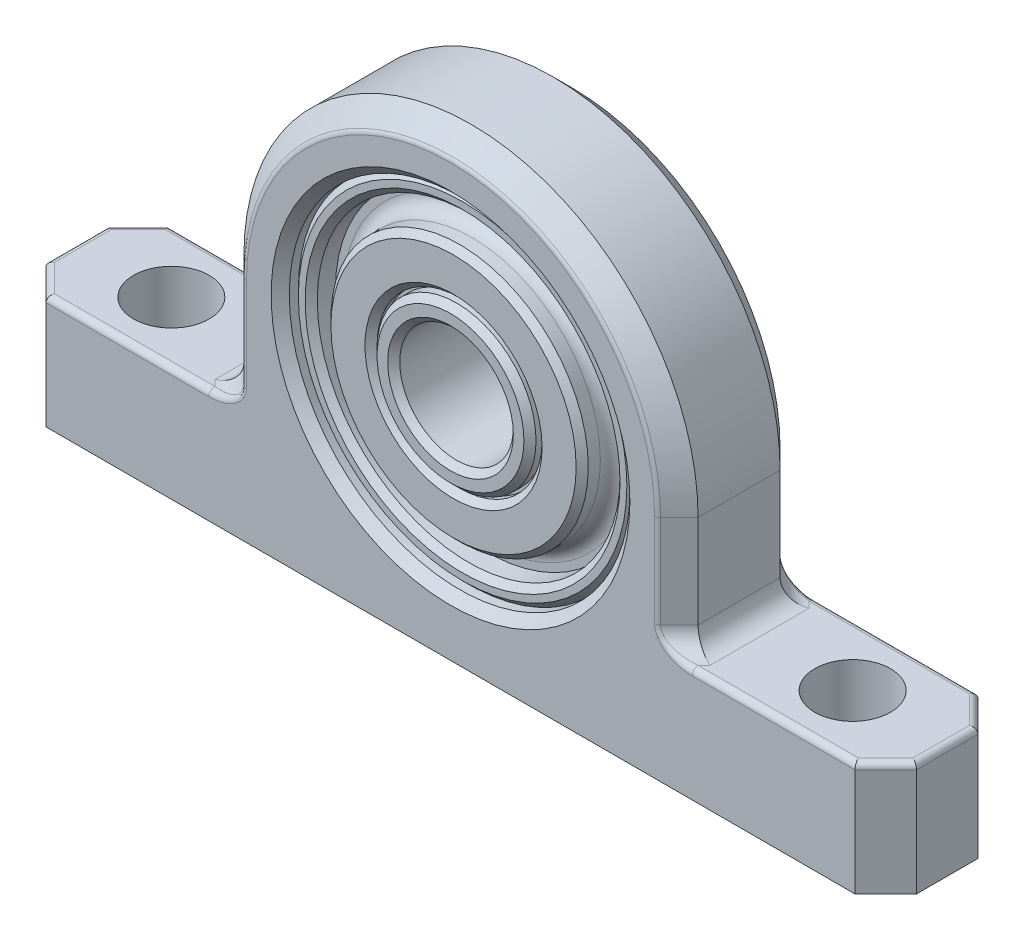
SolidWorks part; units mm, degrees
ref_plane "Front Plane" through (0, 0, 0) normal (0, 0, 1) x (1, 0, 0)
ref_plane "Top Plane" through (0, 0, 0) normal (0, 1, 0) x (1, 0, 0)
ref_plane "Right Plane" through (0, 0, 0) normal (1, 0, 0) x (0, 0, -1)
sketch "Sketch1" plane through (0, 0, 0) normal (0, 0, 1) x (1, 0, 0)
  line L0 (9.525, 0) -> (9.525, -4.7625)
  line L1 (9.525, -4.7625) -> (18.2562, -4.7625)
  line L2 (18.2562, -4.7625) -> (18.2562, -9.525)
  line L3 (18.2562, -9.525) -> (-18.2563, -9.525)
  line L4 (-18.2563, -9.525) -> (-18.2563, -4.7625)
  line L5 (-18.2563, -4.7625) -> (-9.525, -4.7625)
  line L6 (-9.525, -4.7625) -> (-9.525, 0)
  circle A0 centre (0, 0) radius 2.3813
  arc A1 (9.525, 0) -> (-9.525, 0) centre (0, 0) ccw
  circle A2 centre (0, 0) radius 7.1438
  point P12 (0, 7.1438)
  point P13 (0, 2.3813)
  dimension "D1" = 14.2875
sketch "Sketch2" plane through (0, 0, 0) normal (0, 1, 0) x (1, 0, 0)
  line L0 (0, 2.5797) -> (0, -2.5797) construction
  line L1 (-14.2875, 0) -> (14.2875, 0) construction
  circle A0 centre (14.2875, 0) radius 1.5875
  circle A1 centre (-14.2875, 0) radius 1.5875
sketch "Sketch3" plane through (0, 0, 0) normal (0, 0, 1) x (1, 0, 0)
  line L0 (9.525, 0) -> (9.525, -4.7625) construction
  line L1 (18.2562, -4.7625) -> (18.2562, -9.525) construction
  line L2 (9.525, -4.7625) -> (18.2562, -4.7625) construction
  line L3 (18.2562, -9.525) -> (-18.2563, -9.525) construction
  line L4 (-18.2563, -9.525) -> (-18.2563, -4.7625) construction
  line L5 (-18.2563, -4.7625) -> (-9.525, -4.7625) construction
  line L6 (-9.525, -4.7625) -> (-9.525, 0) construction
  line L7 (9.525, 0) -> (9.525, -4.7625)
  line L8 (18.2562, -4.7625) -> (18.2562, -9.525)
  line L9 (9.525, -4.7625) -> (18.2562, -4.7625)
  line L10 (18.2562, -9.525) -> (-18.2563, -9.525)
  line L11 (-18.2563, -9.525) -> (-18.2563, -4.7625)
  line L12 (-18.2563, -4.7625) -> (-9.525, -4.7625)
  line L13 (-9.525, -4.7625) -> (-9.525, 0)
  arc A0 (9.525, 0) -> (-9.525, 0) centre (0, 0) ccw construction
  circle A1 centre (0, 0) radius 7.1438 construction
  arc A2 (9.525, 0) -> (-9.525, 0) centre (0, 0) ccw
  circle A3 centre (0, 0) radius 7.1438
extrude "Extrude1" add sketch "Sketch3" along normal up to vertex (2.5797 mm away) and the other way up to vertex (2.5797 mm away) up to point (0, 0, 2.5797) other way up to point (0, 0, -2.5797)
sketch "Sketch4" plane through (0, -4.7625, 0) normal (0, 1, 0) x (1, 0, 0)
  line L0 (-18.2563, 2.5797) -> (-18.2563, 1.2898)
  line L1 (-18.2563, -2.5797) -> (-18.2563, 2.5797) construction
  line L2 (-18.2563, 1.2898) -> (-16.9664, 2.5797)
  line L3 (-9.525, 2.5797) -> (-18.2563, 2.5797) construction
  line L4 (-16.9664, 2.5797) -> (-18.2563, 2.5797)
  line L5 (0, 0) -> (0, 2.5797) construction
  line L6 (0, 0) -> (-14.2875, 0) construction
  line L7 (16.9664, 2.5797) -> (18.2563, 2.5797)
  line L8 (18.2563, 1.2898) -> (16.9664, 2.5797)
  line L9 (18.2563, 2.5797) -> (18.2563, 1.2898)
  line L10 (18.2563, -2.5797) -> (18.2563, -1.2898)
  line L11 (18.2563, -1.2898) -> (16.9664, -2.5797)
  line L12 (16.9664, -2.5797) -> (18.2563, -2.5797)
  line L13 (-16.9664, -2.5797) -> (-18.2563, -2.5797)
  line L14 (-18.2563, -1.2898) -> (-16.9664, -2.5797)
  line L15 (-18.2563, -2.5797) -> (-18.2563, -1.2898)
  circle A0 centre (-14.2875, 0) radius 1.5875 construction
  circle A1 centre (14.2875, 0) radius 1.5875 construction
  circle A2 centre (-14.2875, 0) radius 1.5875
  circle A3 centre (14.2875, 0) radius 1.5875
  dimension "D1" = 45
  dimension "D2" = 1.2898
extrude "Cut-Extrude1" cut sketch "Sketch4" against normal through all
chamfer "Chamfer3" distance 0.8599 angle 45 6 edges at (-9.525, -2.3812, -2.5797) (0, 9.525, -2.5797) (9.525, -2.3812, -2.5797) (-9.525, -2.3812, 2.5797) (0, 9.525, 2.5797) (9.525, -2.3812, 2.5797)
fillet "Fillet6" radius 0.8599 6 edges at (9.525, -4.7625, 0) (9.0951, -4.7625, -2.1497) (9.0951, -4.7625, 2.1497) (-9.0951, -4.7625, -2.1497) (-9.0951, -4.7625, 2.1497) (-9.525, -4.7625, 0)
fillet "Fillet7" radius 0.254 20 edges at (13.4238, -4.7625, -2.5797) (9.0213, -4.5106, -2.5797) (8.6651, -1.9513, -2.5797) (0, 8.6651, -2.5797) (-8.6651, -1.9513, -2.5797) (-9.0213, -4.5106, -2.5797) (13.4238, -4.7625, 2.5797) (9.0213, -4.5106, 2.5797) (8.6651, -1.9513, 2.5797) (0, 8.6651, 2.5797) (-8.6651, -1.9513, 2.5797) (-9.0213, -4.5106, 2.5797) (17.6113, -4.7625, 1.9348) (18.2563, -4.7625, 0) (17.6113, -4.7625, -1.9348) (-13.4238, -4.7625, -2.5797) (-17.6113, -4.7625, -1.9348) (-18.2563, -4.7625, 0) (-17.6113, -4.7625, 1.9348) (-13.4238, -4.7625, 2.5797)
chamfer "Chamfer4" distance 0.381 angle 45 2 edges at (7.1438, 0, -2.5797) (7.1438, 0, 2.5797)
sketch "Sketch5" plane through (0, 0, 0) normal (1, 0, 0) x (0, 0, -1)
  line L0 (-2.0717, 6.35) -> (-1.0557, 6.35)
  line L3 (0, 0) -> (-2.5797, 0) construction
  line L4 (2.5797, 3.3338) -> (2.5797, 2.3813)
  line L5 (-1.0557, 6.35) -> (-1.0557, 5.3975)
  line L6 (-1.0557, 5.3975) -> (-2.4527, 5.3975)
  line L7 (-1.9447, 3.3338) -> (-1.9447, 3.4608)
  line L8 (-2.5797, 2.3813) -> (2.5797, 2.3813)
  line L9 (-1.9447, 3.3338) -> (-2.5797, 3.3338)
  line L10 (-2.0717, 7.1438) -> (2.0717, 7.1438)
  line L12 (-2.5797, 3.3338) -> (-2.5797, 2.3813)
  line L13 (-2.0717, 7.1438) -> (-2.0717, 6.35)
  line L14 (-2.5797, -9.525) -> (-2.5797, -5.0165) construction
  line L15 (-1.9447, 3.4608) -> (-2.4527, 3.4608)
  line L16 (-2.4527, 3.4608) -> (-2.4527, 5.3975)
  line L17 (0, 7.1438) -> (0, 9.525) construction
  line L18 (0, 9.525) -> (0, 0) construction
  line L19 (2.4527, 3.4608) -> (2.4527, 5.3975)
  line L20 (1.9447, 3.4608) -> (2.4527, 3.4608)
  line L21 (2.0717, 7.1438) -> (2.0717, 6.35)
  line L22 (1.9447, 3.3338) -> (2.5797, 3.3338)
  line L23 (1.9447, 3.3338) -> (1.9447, 3.4608)
  line L24 (1.0557, 5.3975) -> (2.4527, 5.3975)
  line L25 (1.0557, 6.35) -> (1.0557, 5.3975)
  line L26 (2.0717, 6.35) -> (1.0557, 6.35)
  line L27 (1.7198, 9.525) -> (-1.7198, 9.525) construction
  dimension "D1" = 4.7625
  dimension "D2" = 0.7938
  dimension "D3" = 0.9525
  dimension "D4" = 6.6675
  dimension "D6" = 1.016
  dimension "D5" = 0.635
  dimension "D7" = 0.127
  dimension "D8" = 0.127
  dimension "D9" = 0.508
revolve "Revolve1" add sketch "Sketch5" angle 360 about L0
chamfer "Chamfer5" distance 0.254 angle 45 12 edges at (-2.3813, 0, -2.5797) (-3.3338, 0, -2.5797) (-3.3337, 0, 2.5797) (-2.3812, 0, 2.5797) (-3.4608, 0, -2.4527) (-5.3975, 0, -2.4527) (-5.3975, 0, 2.4527) (-3.4608, 0, 2.4527) (-6.35, 0, -2.0717) (-7.1438, 0, -2.0717) (-7.1437, 0, 2.0717) (-6.35, 0, 2.0717)
fillet "Fillet8" radius 0.635 2 edges at (-5.3975, 0, -1.0557) (-5.3975, 0, 1.0557)
equation "\"D1@Sketch1\"=\"I@Sketch1\"*.75"
equation "\"D2@Sketch4\" = \"E@Sketch2\"/4"
equation "\"D1@Chamfer3\"=\"E@Sketch2\"/6"
equation "\"D1@Fillet6\"=\"D1@Chamfer3\""
equation "\"D2@Sketch5\"=\"D1@Sketch5\"/6"
equation "\"D3@Sketch5\"=\"D2@Sketch5\"*1.2"
equation "\"D4@Sketch5\"=\"shaft dia@Sketch1\"*1.4"
